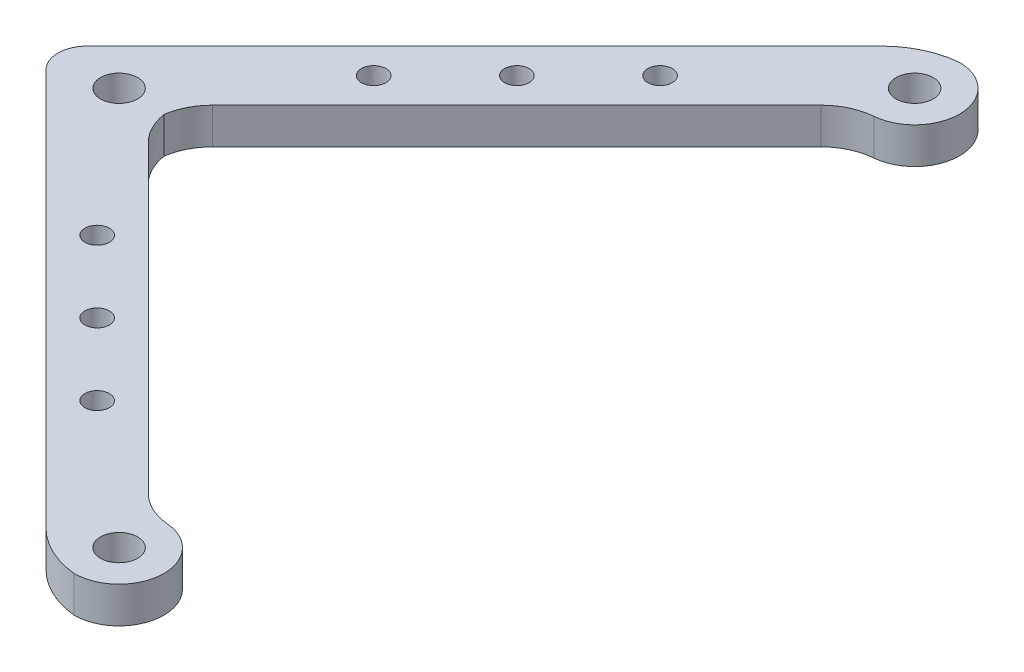
SolidWorks part; units mm, degrees
material "support_V_mat"
ref_plane "Front Plane" through (0, 0, 0) normal (0, 0, 1) x (1, 0, 0)
ref_plane "Top Plane" through (0, 0, 0) normal (0, 1, 0) x (1, 0, 0)
ref_plane "Right Plane" through (0, 0, 0) normal (1, 0, 0) x (0, 0, -1)
sketch "Sketch1" plane through (0, 0, 0) normal (0, 1, 0) x (1, 0, 0)
  line L4 (0, 0) -> (-125.5226, 0) construction
  line L5 (0, 0) -> (0, -105.5552) construction
  line L6 (-82.6777, 0) -> (0, -82.677)
  line L7 (0, -82.677) -> (0, -64.7166)
  line L8 (0, -64.7166) -> (-64.7172, 0)
  line L9 (-64.7172, 0) -> (-82.6777, 0)
  dimension "D1" = 12.7
  dimension "D2" = 116.9235
extrude "Boss-Extrude2" add sketch "Sketch1" along normal blind 6.35
mirror "Mirror1" about plane through (0, 0, 0) normal (0, 0, 1) of "Boss-Extrude2"
sketch "Sketch6" plane through (0, 6.35, 0) normal (0, 1, 0) x (1, 0, 0)
  circle A0 centre (0, -69.85) radius 7.874
  dimension "D1" = 69.85
extrude "Boss-Extrude3" add sketch "Sketch6" against normal blind 6.35
hole_wizard "F (0.257) Diameter Hole1" positions "Sketch4" profile "Sketch5" hole size "F" standard "ANSI Inch"
sketch "Sketch4" plane through (0, 6.35, 0) normal (0, 1, 0) x (1, 0, 0)
  circle A0 centre (0, -69.85) radius 9.525
  point P0 (0, -69.85)
  dimension "D2" = 19.05
  dimension "D1" = 69.85
sketch "Sketch5" plane through (0, 6.35, 69.85) normal (1, 0, 0) x (0, 0, 1)
  line L0 (0, 0) -> (0, 52.7611)
  line L1 (0, 52.7611) -> (3.2639, 50.8)
  line L2 (3.2639, 50.8) -> (3.2639, 0)
  line L5 (3.2639, 0) -> (0, 0)
  line L10 (0, 52.7611) -> (-3.2639, 50.8) construction
  line L11 (0, -6.35) -> (0, 107.95) construction
  dimension "Hole Dia." = 6.5278
  dimension "Hole Depth" = 50.8
  dimension "Drill Angle" = 118
ref_axis "Axis1" through (0, 0, 0) along (0, 1, 0)
pattern_circular "CirPattern1" count 3 over 180 about axis through (0, 0, 0) along (0, 1, 0) of "F (0.257) Diameter Hole1", "Boss-Extrude3" reverse direction yes
sketch "Sketch7" plane through (0, 6.35, 0) normal (0, 1, 0) x (1, 0, 0)
  line L1 (-82.6777, 0) -> (0, -82.677) construction
  line L2 (-36.8488, -36.8484) -> (-41.3389, -41.3385) construction
  line L4 (-49.4211, -24.276) -> (-24.2764, -49.4207) construction
  circle A0 centre (-36.8488, -36.8484) radius 2.1527
  circle A1 centre (-49.4211, -24.276) radius 2.1526
  circle A2 centre (-24.2764, -49.4207) radius 2.1527
  point P8 (-36.8488, -36.8484)
  dimension "D1" = 4.3053
  dimension "D4" = 4.3053
  dimension "D5" = 4.3053
  dimension "D2" = 6.35
  dimension "D3" = 35.56
extrude "Cut-Extrude1" cut sketch "Sketch7" against normal through all
mirror "Mirror2" about plane through (0, 0, 0) normal (0, 0, 1) of "Cut-Extrude1"
fillet "Fillet1" radius 15.24 2 edges at (0, 3.175, 82.677) (0, 3.175, -82.677)
fillet "Fillet2" radius 10.16 4 edges at (-62.3426, 3.175, 2.3746) (-62.3426, 3.175, -2.3746) (-2.3741, 3.175, -62.3424) (-2.3741, 3.175, 62.3424)
fillet "Fillet3" radius 5.08 1 edges at (-82.6777, 3.175, 0)
